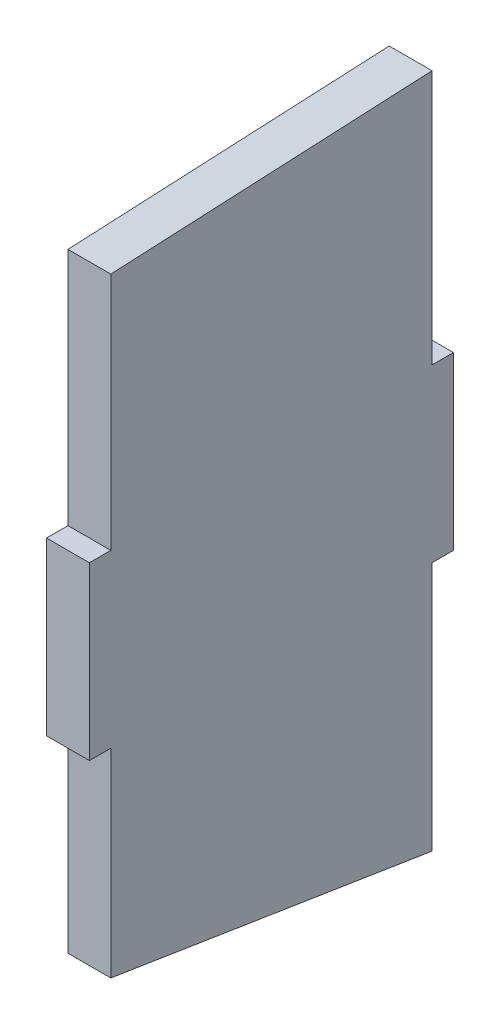
SolidWorks part; units mm, degrees
material "Pink Foam"
ref_plane "Front Plane" through (0, 0, 0) normal (0, 0, 1) x (1, 0, 0)
ref_plane "Top Plane" through (0, 0, 0) normal (0, 1, 0) x (1, 0, 0)
ref_plane "Right Plane" through (0, 0, 0) normal (1, 0, 0) x (0, 0, -1)
sketch "Sketch1" plane through (0, 0, 0) normal (1, 0, 0) x (0, 0, -1)
  line L0 (-95.25, 192.6958) -> (95.25, 201.8798)
  line L1 (-95.25, -203.2) -> (95.25, -203.2)
  line L2 (-95.25, -203.2) -> (-95.25, 203.2)
  line L3 (-95.25, 203.2) -> (95.25, 203.2)
  line L4 (95.25, -203.2) -> (95.25, 203.2)
  line L5 (-95.25, -203.2) -> (95.25, 203.2) construction
  line L6 (-95.25, 203.2) -> (95.25, -203.2) construction
  line L7 (-107.95, -50.8) -> (107.95, -50.8)
  line L8 (-107.95, -50.8) -> (-107.95, 50.8)
  line L9 (-107.95, 50.8) -> (107.95, 50.8)
  line L10 (107.95, -50.8) -> (107.95, 50.8)
  line L11 (-107.95, -50.8) -> (107.95, 50.8) construction
  line L12 (-107.95, 50.8) -> (107.95, -50.8) construction
  line L14 (-95.25, -168.8002) -> (95.25, -198.8953)
  point P0 (0, 0)
  point P6 (0, 0)
  dimension "D1" = 190.5
  dimension "D2" = 215.9
  dimension "D3" = 101.6
  dimension "D4" = 406.4
  dimension "D5" = 10.5042
  dimension "D6" = 1.3202
  dimension "D7" = 4.3047
  dimension "D8" = 361.496
extrude "Boss-Extrude1" add sketch "Sketch1" along normal blind 25.4 contours L2 L9 L4 L0 | L7 L10 L9 L4 | L9 L2 L7 L4 | L9 L8 L7 L2 | L2 L14 L4 L7 region at (0, 124.0679, -0.9953) region at (0, 0, 0) region at (0, 0, 101.6) region at (0, 0, -101.6) region at (0, -117.6075, -3.5909)
